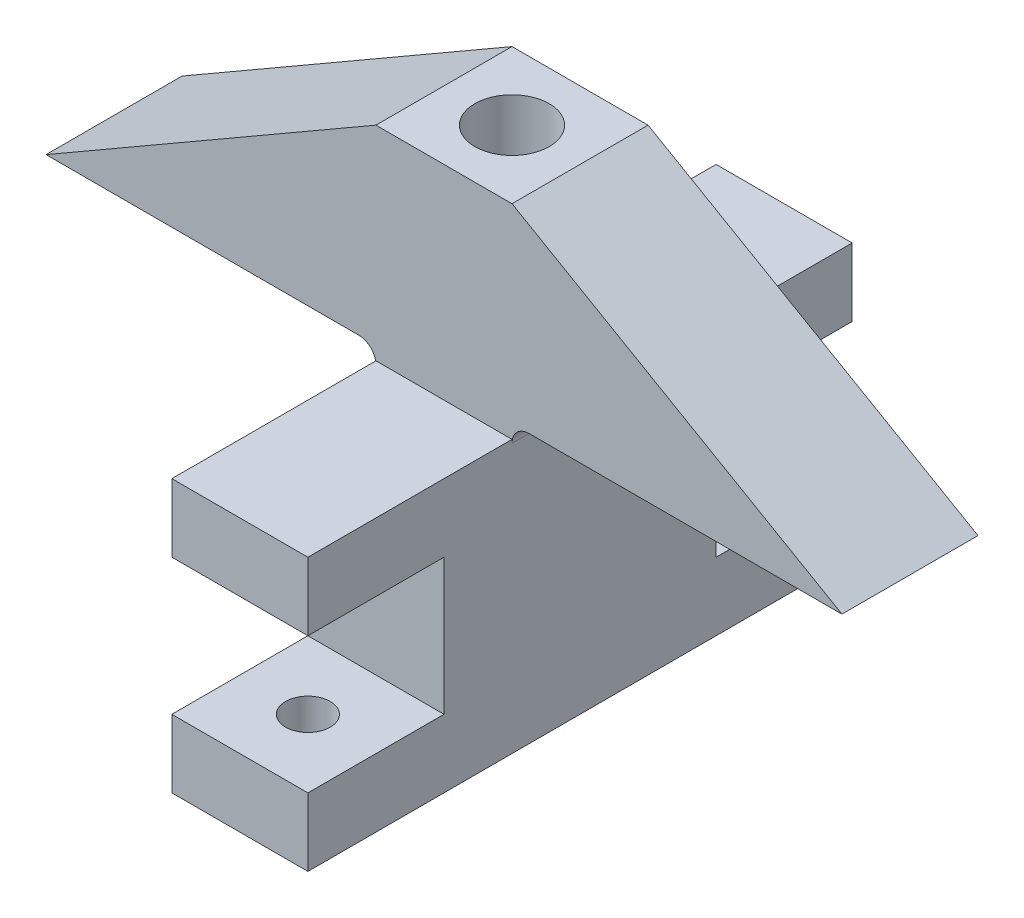
SolidWorks part; units mm, degrees
material "PET"
ref_plane "Front Plane" through (0, 0, 0) normal (0, 0, 1) x (1, 0, 0)
ref_plane "Top Plane" through (0, 0, 0) normal (0, 1, 0) x (1, 0, 0)
ref_plane "Right Plane" through (0, 0, 0) normal (1, 0, 0) x (0, 0, -1)
sketch "Sketch1" plane through (0, 0, 0) normal (0, 0, 1) x (1, 0, 0)
  line L0 (0, 0) -> (0, 53.34)
  line L1 (0, 53.34) -> (-61.5917, 53.34)
  line L2 (-61.5917, 53.34) -> (0, 88.9)
  line L3 (0, 88.9) -> (25.4, 88.9)
  line L4 (25.4, 88.9) -> (86.9917, 53.34)
  line L5 (86.9917, 53.34) -> (25.4, 53.34)
  line L6 (25.4, 53.34) -> (25.4, 0)
  line L7 (25.4, 0) -> (0, 0)
  point P9 (12.7, 88.9)
  point P10 (12.7, 0)
  dimension "D1" = 35.56
  dimension "D2" = 25.4
  dimension "D3" = 30
  dimension "D4" = 30
  dimension "D5" = 25.4
  dimension "D6" = 88.9
extrude "Boss-Extrude1" add sketch "Sketch1" along normal blind 25.4
sketch "Sketch2" plane through (0, 0, 25.4) normal (0, 0, 1) x (1, 0, 0)
  line L1 (0, 0) -> (25.4, 0)
  line L2 (0, 0) -> (0, 12.7)
  line L3 (0, 12.7) -> (25.4, 12.7)
  line L4 (25.4, 0) -> (25.4, 12.7)
  line L5 (25.4, 0) -> (25.4, 53.34) construction
  dimension "D1" = 12.7
extrude "Boss-Extrude2" add sketch "Sketch2" along normal blind 38.1
sketch "Sketch3" plane through (0, 0, 0) normal (0, 0, -1) x (-1, 0, 0)
  line L1 (-25.4, 0) -> (0, 0)
  line L2 (-25.4, 0) -> (-25.4, 12.7)
  line L3 (-25.4, 12.7) -> (0, 12.7)
  line L4 (0, 0) -> (0, 12.7)
  line L5 (0, 53.34) -> (0, 0) construction
  point P5 (0, 0)
  dimension "D1" = 12.7
extrude "Boss-Extrude3" add sketch "Sketch3" along normal blind 38.1
hole_wizard "Ø0.328in Dowel Hole1" positions "Sketch4" profile "Sketch5" hole size "Ø1.0" standard "ISO" end condition through all
sketch "Sketch4" plane through (0, 12.7, 0) normal (0, 1, 0) x (1, 0, 0)
  point P0 (12.7, 25.4)
  point P2 (12.7, -50.8)
  dimension "D1" = 12.7
  dimension "D2" = 12.7
  dimension "D3" = 12.7
  dimension "D4" = 12.7
sketch "Sketch5" plane through (12.7, 12.7, -25.4) normal (1, 0, 0) x (0, 0, 1)
  line L0 (0, 0) -> (0, 12.7)
  line L1 (0, 12.7) -> (4.1656, 12.7)
  line L2 (4.1656, 12.7) -> (4.1656, 0)
  line L5 (4.1656, 0) -> (0, 0)
  line L11 (0, -6.35) -> (0, 107.95) construction
  dimension "Thru Hole Dia." = 8.3312
  dimension "Thru Hole Depth" = 12.7
hole_wizard "Ø0.55in Dowel Hole2" positions "Sketch7" profile "Sketch6" hole size "Ø1.0" standard "ISO"
sketch "Sketch7" plane through (0, 88.9, 0) normal (0, 1, 0) x (1, 0, 0)
  point P0 (12.7, -12.7)
  dimension "D1" = 12.7
  dimension "D2" = 12.7
sketch "Sketch6" plane through (12.7, 88.9, 12.7) normal (1, 0, 0) x (0, 0, 1)
  line L0 (0, 0) -> (0, 39.2261)
  line L1 (0, 39.2261) -> (6.9469, 35.052)
  line L2 (6.9469, 35.052) -> (6.9469, 0)
  line L5 (6.9469, 0) -> (0, 0)
  line L10 (0, 39.2261) -> (-6.9469, 35.052) construction
  line L11 (0, -6.35) -> (0, 107.95) construction
  dimension "Hole Dia." = 13.8938
  dimension "Hole Depth" = 35.052
  dimension "Drill Angle" = 118
fillet "Fillet1" radius 3.175 2 edges at (25.4, 53.34, 12.7) (0, 53.34, 12.7)
sketch "Sketch8" plane through (0, 0, 25.4) normal (0, 0, 1) x (1, 0, 0)
  line L0 (25.4, 12.7) -> (25.4, 50.165) construction
  line L1 (0, 12.7) -> (25.4, 12.7)
  line L2 (0, 12.7) -> (0, 50.8)
  line L3 (0, 50.8) -> (25.4, 50.8)
  line L4 (25.4, 12.7) -> (25.4, 50.8)
  line L5 (0, 38.1) -> (25.4, 38.1)
  line M5 (0, 12.7) -> (25.4, 12.7)
  line M6 (25.4, 12.7) -> (25.4, 50.165)
  line M14 (0, 50.165) -> (0, 12.7)
  dimension "D1" = 38.1
  dimension "D2" = 25.4
extrude "Boss-Extrude4" add sketch "Sketch8" along normal blind 12.7 contours L5 L2 M5 M6 region at (12.7, 25.4, 25.4)
extrude "Boss-Extrude5" add sketch "Sketch8<3>" along normal blind 38.1 contours L5 L4 L3 L2 M14 region at (12.7, 44.45, 25.4)
sketch "Sketch8<3>" plane through (0, 0, 25.4) normal (0, 0, 1) x (1, 0, 0) same geometry as "Sketch8"
sketch "Sketch9" plane through (0, 0, 0) normal (0, 0, -1) x (-1, 0, 0)
  line L0 (-25.4, 38.1) -> (0, 38.1)
  line L1 (-25.4, 12.7) -> (0, 12.7)
  line L2 (-25.4, 12.7) -> (-25.4, 50.8)
  line L3 (-25.4, 50.8) -> (0, 50.8)
  line L4 (0, 12.7) -> (0, 50.8)
  line L5 (0, 38.1) -> (0, 12.7) construction
  point P7 (0, 0)
  line M6 (-25.4, 12.7) -> (0, 12.7)
  line M7 (0, 12.7) -> (0, 50.165)
  line M15 (-25.4, 50.165) -> (-25.4, 12.7)
  dimension "D1" = 25.4
  dimension "D2" = 38.1
extrude "Boss-Extrude6" add sketch "Sketch9" along normal blind 12.7 contours L0 M15 M6 M7 region at (12.7, 25.4, 0)
extrude "Boss-Extrude7" add sketch "Sketch9<3>" along normal blind 38.1 contours L4 L3 L2 L0 M7 M15 region at (12.7, 44.45, 0)
sketch "Sketch9<3>" plane through (0, 0, 0) normal (0, 0, -1) x (-1, 0, 0) same geometry as "Sketch9"
